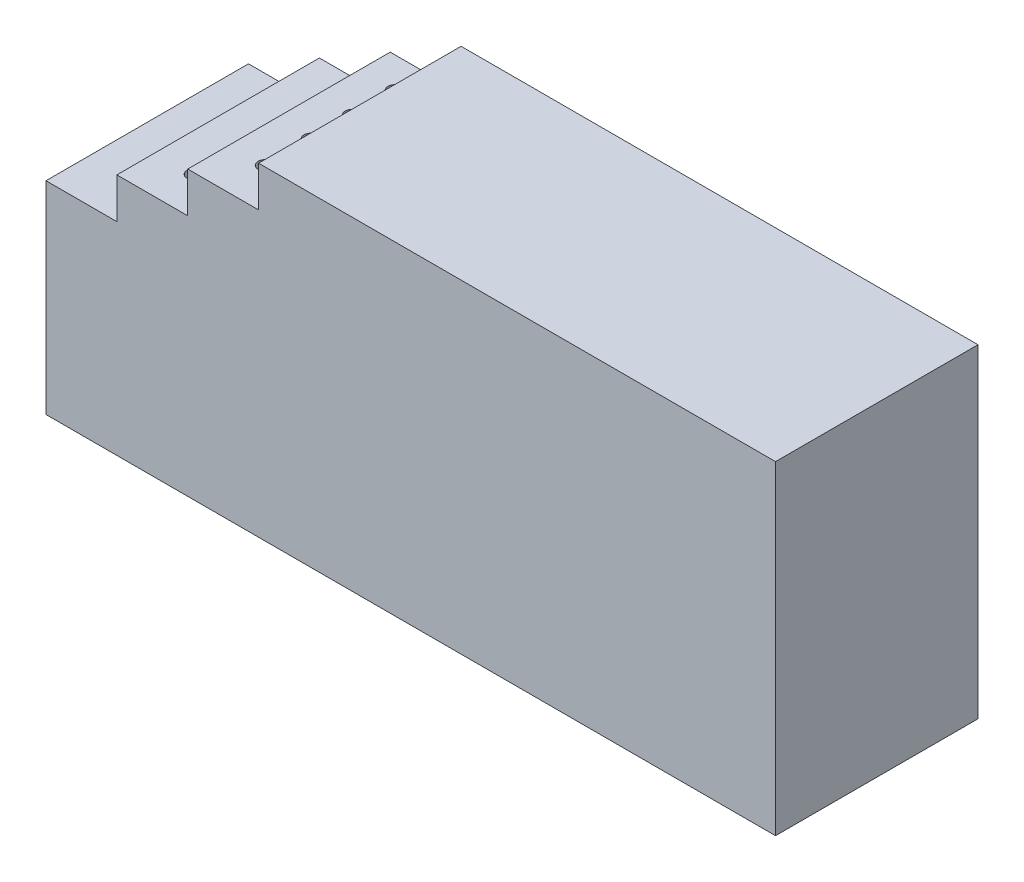
SolidWorks part; units mm, degrees
material "granite"
ref_plane "Front Plane" through (0, 0, 0) normal (0, 0, 1) x (1, 0, 0)
ref_plane "Top Plane" through (0, 0, 0) normal (0, 1, 0) x (1, 0, 0)
ref_plane "Right Plane" through (0, 0, 0) normal (1, 0, 0) x (0, 0, -1)
sketch "Эскиз1" plane through (0, 0, 0) normal (0, 1, 0) x (1, 0, 0)
  line L0 (300.279, 100) -> (300.279, 0)
  line L1 (0, 0) -> (360.279, 0)
  line L2 (0, 0) -> (0, 100)
  line L3 (0, 100) -> (360.279, 100)
  line L4 (360.279, 0) -> (360.279, 100)
  line L5 (35, 100) -> (35, 0)
  line L6 (70, 100) -> (70, 0)
  line L7 (105, 100) -> (105, 0)
  dimension "D1" = 35
  dimension "D2" = 35
  dimension "D3" = 35
  dimension "D4" = 60
  dimension "D5" = 100
extrude "Бобышка-Вытянуть1" add sketch "Эскиз1" along normal blind 100 contours L5 L3 L2 L1 region at (17.5, 0, -50)
extrude "Бобышка-Вытянуть2" add sketch "Эскиз1<3>" along normal blind 120 contours L6 L3 L5 L1 region at (52.5, 0, -50)
sketch "Эскиз1<3>" plane through (0, 0, 0) normal (0, 1, 0) x (1, 0, 0) same geometry as "Эскиз1"
extrude "Бобышка-Вытянуть3" add sketch "Эскиз1<4>" along normal blind 140 contours L7 L3 L6 L1 region at (87.5, 0, -50)
sketch "Эскиз1<4>" plane through (0, 0, 0) normal (0, 1, 0) x (1, 0, 0) same geometry as "Эскиз1"
extrude "Бобышка-Вытянуть4" add sketch "Эскиз1<5>" along normal blind 160 contours L3 L7 L1 L0 region at (202.6395, 0, -50)
sketch "Эскиз1<5>" plane through (0, 0, 0) normal (0, 1, 0) x (1, 0, 0) same geometry as "Эскиз1"
extrude "Бобышка-Вытянуть5" add sketch "Эскиз1<6>" along normal blind 160 contours L1 L4 L3 L0 region at (330.279, 0, -50)
sketch "Эскиз1<6>" plane through (0, 0, 0) normal (0, 1, 0) x (1, 0, 0) same geometry as "Эскиз1"
sketch "Эскиз4" plane through (0, 100, 0) normal (0, 1, 0) x (1, 0, 0)
  circle A0 centre (17.5, 79.0184) radius 3.5
  circle A1 centre (17.5, 57.8618) radius 3.5
  circle A2 centre (17.5, 37.503) radius 3.5
  circle A3 centre (17.5, 14.8722) radius 3.5
sketch "Эскиз7" plane through (0, 100, 0) normal (0, 1, 0) x (1, 0, 0)
sketch "Эскиз10" plane through (0, 140, 0) normal (0, 1, 0) x (1, 0, 0)
sketch "Эскиз11" plane through (0, 120, 0) normal (0, 1, 0) x (1, 0, 0)
sketch "Эскиз12" plane through (0, 120, 0) normal (0, 1, 0) x (1, 0, 0)
  circle A0 centre (59.7752, 81.3175) radius 1.6397
  circle A1 centre (44.7466, 79.6778) radius 1.2404
  circle A2 centre (52.3373, 73.2112) radius 1.6397
  circle A3 centre (45.987, 58.3885) radius 1.7674
  circle A7 centre (44.2196, 24.4761) radius 1.5659
  circle A8 centre (62.788, 69.7525) radius 0.6029
  circle A9 centre (62.788, 60.5423) radius 0.6867
  circle A10 centre (63.4747, 41.0197) radius 0.861
  circle A11 centre (63.4747, 27.5473) radius 0.9191
  circle A12 centre (64.3938, 14.8827) radius 1.1125
  circle A13 centre (101.6013, 78.2083) radius 1.112
  circle A14 centre (88.8982, 85.5663) radius 0.7516
  circle A15 centre (89.6498, 74.1032) radius 0.9913
  circle A16 centre (96.0182, 61.9915) radius 1.4535
  circle A17 centre (96.0182, 47.378) radius 0.9191
  circle A18 centre (83.8598, 51.1908) radius 0.8052
  circle A19 centre (85.5445, 35.7584) radius 1.237
  circle A20 centre (93.2502, 17.536) radius 1.237
sketch "Эскиз13" plane through (0, 160, 0) normal (0, 1, 0) x (1, 0, 0)
  circle A0 centre (121.889, 81.1917) radius 1.4807
  circle A1 centre (123.3697, 67.9277) radius 0.8385
  circle A2 centre (125.0127, 54.4098) radius 0.9704
  circle A3 centre (116.9108, 42.599) radius 0.7271
  circle A4 centre (148.1772, 60.5998) radius 1.0243
  circle A5 centre (145.5601, 29.9428) radius 0.6358
  circle A6 centre (132.5977, 20.9135) radius 1.7896
  circle A7 centre (173.4445, 20.9135) radius 2.1032
  circle A8 centre (173.4445, 60.5998) radius 1.7853
  circle A9 centre (196.7277, 58.8145) radius 0.9529
  circle A10 centre (202.9352, 33.1493) radius 0.8948
  circle A11 centre (217.5035, 81.1917) radius 0.3379
  circle A12 centre (240.0338, 81.1917) radius 0.1263
  circle A13 centre (181.8949, 85.9498) radius 0.5471
  circle A14 centre (240.0338, 33.1493) radius 1.182
  circle A15 centre (266.792, 23.0167) radius 2.1157
  circle A16 centre (264.6763, 65.1023) radius 1.6136
sketch "Эскиз16" plane through (0, 160, 0) normal (0, 1, 0) x (1, 0, 0)
  circle A0 centre (307.2749, 85.3342) radius 1.1163
  circle A1 centre (317.267, 78.1038) radius 1.3337
  circle A2 centre (327.284, 53.6199) radius 1.1114
  circle A3 centre (317.267, 49.7954) radius 1.5425
  circle A4 centre (308.3912, 38.0748) radius 1.6713
  circle A5 centre (310.0625, 19.0381) radius 1.1208
  circle A6 centre (334.3354, 19.0381) radius 0.2692
  circle A7 centre (341.7204, 33.2906) radius 1.2966
  circle A8 centre (347.508, 62.9461) radius 1.133
sketch "Эскиз17" plane through (0, 120, 0) normal (0, 1, 0) x (1, 0, 0)
  circle A0 centre (53.8591, 83.4584) radius 3.5
  circle A1 centre (53.8591, 62.3017) radius 3.5
  circle A2 centre (53.8591, 41.9429) radius 3.5
  circle A3 centre (53.8591, 19.3121) radius 3.5
extrude "Вырез-Вытянуть4" cut sketch "Эскиз17" against normal blind 25
sketch "Эскиз18" plane through (0, 140, 0) normal (0, 1, 0) x (1, 0, 0)
  circle A0 centre (87.5722, 84.8536) radius 3.5
  circle A1 centre (87.5722, 63.6969) radius 3.5
  circle A2 centre (87.5722, 43.3381) radius 3.5
  circle A3 centre (87.5722, 20.7073) radius 3.5
extrude "Вырез-Вытянуть5" cut sketch "Эскиз18" against normal blind 25
